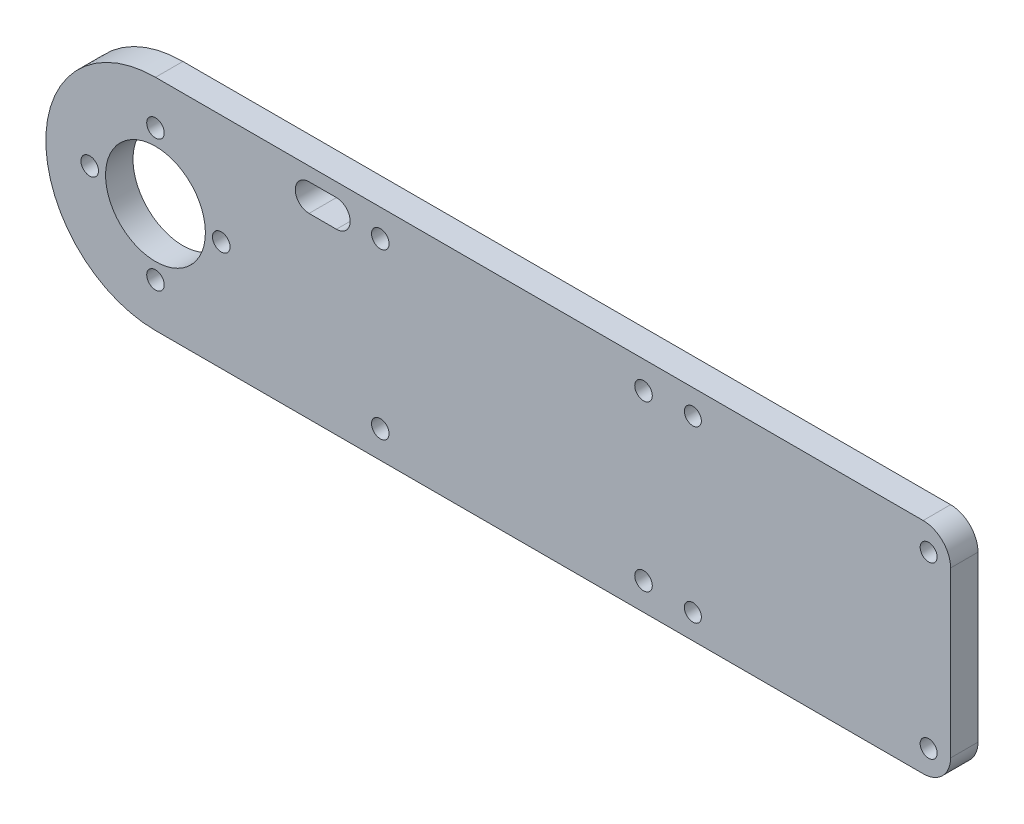
SolidWorks part; units mm, degrees
material "Acrylic (Medium-high impact)"
ref_plane "Front Plane" through (0, 0, 0) normal (0, 0, 1) x (1, 0, 0)
ref_plane "Top Plane" through (0, 0, 0) normal (0, 1, 0) x (1, 0, 0)
ref_plane "Right Plane" through (0, 0, 0) normal (1, 0, 0) x (0, 0, -1)
sketch "Sketch2" plane through (0, 0, 0) normal (0, 0, 1) x (1, 0, 0)
  line L0 (0, 20) -> (0, -20)
  line L1 (0, 20) -> (145, 20)
  line L2 (0, -20) -> (145, -20)
  line L3 (145, 20) -> (145, -20)
  line L4 (0, 0) -> (-20, 0)
  circle A0 centre (0, 0) radius 20
  circle A1 centre (0, 0) radius 9.1
  dimension "D1" = 40
  dimension "D3" = 18.2
  dimension "D2" = 165
extrude "Boss-Extrude1" add sketch "Sketch2" along normal mid plane 5 contours A1 L0 A0 | A0 L2 L3 L1 | A1 L4 A0 L0 | A1 L0 A0 L4 region at (9.696, 0, 0) region at (80.2769, 0, 0) region at (-9.696, 9.696, 0) region at (-9.696, -9.696, 0)
fillet "Fillet1" radius 5 2 edges at (145, -20, 0) (145, 20, 0)
sketch "Sketch3" plane through (0, 0, -2.5) normal (0, 0, -1) x (-1, 0, 0)
  line L0 (-119.5, 20) -> (-119.5, -20)
  line L1 (-119.5, 0) -> (-98, 0)
  line L2 (-98, 0) -> (-98, 15.5)
  line L3 (-145, 15) -> (-145, -15)
  line L4 (-140, -20) -> (0, -20)
  line L5 (0, 20) -> (-140, 20)
  line L6 (-145, 15) -> (-145, -15)
  line L7 (-140, -20) -> (0, -20)
  line L8 (0, 20) -> (-140, 20)
  line L9 (-119.5, 0) -> (-65, 0)
  line L10 (-65, 0) -> (-65, 15)
  line L11 (-65, 15) -> (-89, 15)
  line L12 (0, 0) -> (0, 12)
  line L13 (-41, 15) -> (-33, 15)
  line L14 (-33, 15) -> (-28, 15) construction
  line L17 (-33, 17.5) -> (-28, 17.5)
  line L18 (-33, 12.5) -> (-28, 12.5)
  circle A0 centre (0, 0) radius 12
  circle A1 centre (-98, 15.5) radius 1.55
  circle A2 centre (-98, -15.5) radius 1.55
  arc A3 (-145, -15) -> (-140, -20) centre (-140, -15) ccw
  arc A4 (0, -20) -> (0, 20) centre (0, 0) ccw
  arc A5 (-140, 20) -> (-145, 15) centre (-140, 15) ccw
  arc A6 (-145, -15) -> (-140, -20) centre (-140, -15) ccw
  arc A7 (0, -20) -> (0, 20) centre (0, 0) ccw
  arc A8 (-140, 20) -> (-145, 15) centre (-140, 15) ccw
  circle A9 centre (-141, -15.5) radius 1.55
  circle A10 centre (-141, 15.5) radius 1.55
  circle A11 centre (-89, 15) radius 1.6
  circle A12 centre (-89, -15) radius 1.6
  circle A13 centre (-41, -15) radius 1.6
  circle A14 centre (-41, 15) radius 1.6
  circle A15 centre (0, 12) radius 1.6
  circle A16 centre (12, 0) radius 1.6
  circle A17 centre (0, -12) radius 1.6
  circle A18 centre (-12, 0) radius 1.6
  arc A21 (-33, 17.5) -> (-33, 12.5) centre (-33, 15) ccw
  arc A22 (-28, 12.5) -> (-28, 17.5) centre (-28, 15) ccw
  point P35 (-30.5, 15)
  dimension "D2" = 24
  dimension "D6" = 3.1
  dimension "D10" = 3.2
  dimension "D11" = 3.2
  dimension "D13" = 65
  dimension "D3" = 21.5
  dimension "D4" = 15.5
  dimension "D5" = 98
  dimension "D7" = 8
  dimension "D8" = 15
  dimension "D9" = 24
  dimension "D14" = 5
  dimension "D15" = 5
  dimension "D1" = 0
  dimension "D12" = 4
extrude "Cut-Extrude1" cut sketch "Sketch3" against normal through all contours A14 | A13 | A11 | A12 | A0 A16 | A0 A16 | A0 A17 | A2 | A9 | A10 | A1 | A18 | A15 | A17 region at (90.5547, 15, -2.5) region at (-12.6595, 0, -2.5) region at (-11.3021, 0, -2.5) region at (0, -12.6595, -2.5) region at (42.5547, 15, -2.5) region at (89, -15, -2.5) region at (41, -15, -2.5)
extrude "Cut-Extrude2" cut sketch "Sketch3<4>" against normal blind 10 contours L18 A22 L17 A21 region at (30.5, 15, -2.5)
sketch "Sketch3<4>" plane through (0, 0, -2.5) normal (0, 0, -1) x (-1, 0, 0) same geometry as "Sketch3"
